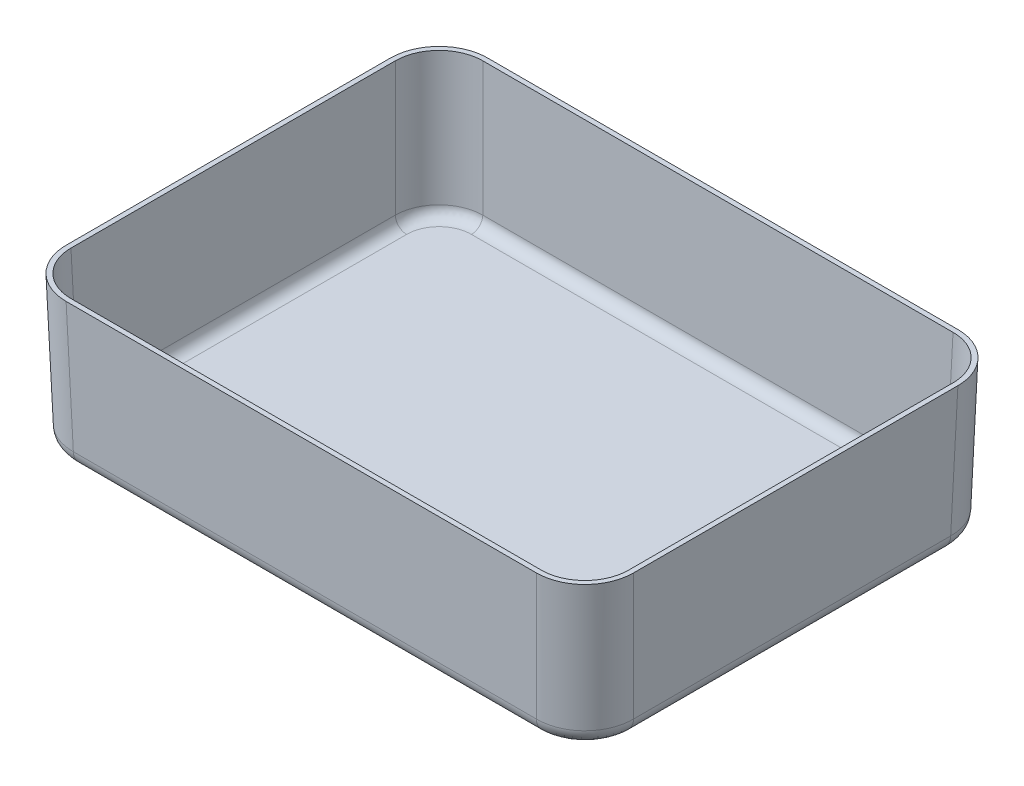
SolidWorks part; units mm, degrees
ref_plane "前基準面" through (0, 0, 0) normal (0, 0, 1) x (1, 0, 0)
ref_plane "上基準面" through (0, 0, 0) normal (0, 1, 0) x (1, 0, 0)
ref_plane "右基準面" through (0, 0, 0) normal (1, 0, 0) x (0, 0, -1)
sketch "草圖1" plane through (0, 0, 0) normal (0, 1, 0) x (1, 0, 0)
  line L1 (-175, -130) -> (175, -130)
  line L2 (-175, -130) -> (-175, 130)
  line L3 (-175, 130) -> (175, 130)
  line L4 (175, -130) -> (175, 130)
  line L5 (-175, -130) -> (175, 130) construction
  line L6 (-175, 130) -> (175, -130) construction
  point P0 (0, 0)
  dimension "D1" = 260
  dimension "D2" = 350
extrude "填料-伸長1" add sketch "草圖1" along normal blind 90
draft "拔模3" type of draft neutral plane draft angle 1.591 faces to draft 4 face at (-175, 45, 0) face at (0, 45, -130) face at (175, 45, 0) face at (0, 45, 130) neutral plane through (0, 90, 0) neutral plane normal (0, 1, 0) reverse direction yes parameters "D1"=1.591
fillet "圓角1" radius 30 4 edges at (173.7501, 45, 128.7501) (-173.7501, 45, 128.7501) (-173.7501, 45, -128.7501) (173.7501, 45, -128.7501)
fillet "圓角3" radius 10 8 edges at (-163.7182, 0, 118.7182) (-172.5002, 0, 0) (-163.7182, 0, -118.7182) (0, 0, -127.5002) (163.7182, 0, -118.7182) (172.5002, 0, 0) (163.7182, 0, 118.7182) (0, 0, 127.5002)
shell "薄殼1" thickness 3 removed face at (0, 90, 0)
